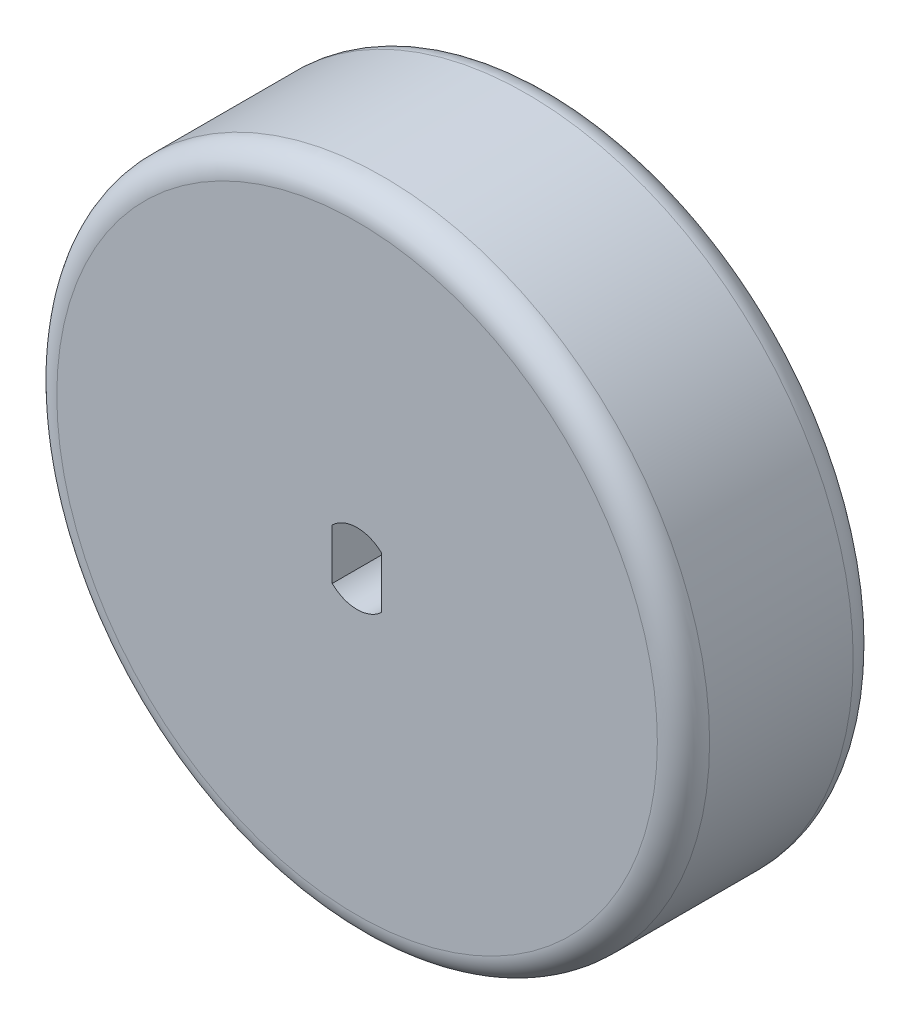
SolidWorks part; units mm, degrees
ref_plane "Front Plane" through (0, 0, 0) normal (0, 0, 1) x (1, 0, 0)
ref_plane "Top Plane" through (0, 0, 0) normal (0, 1, 0) x (1, 0, 0)
ref_plane "Right Plane" through (0, 0, 0) normal (1, 0, 0) x (0, 0, -1)
sketch "Sketch1" plane through (0, 0, 0) normal (0, 0, 1) x (1, 0, 0)
  line L0 (0, 0) -> (0, 25)
  circle A0 centre (0, 0) radius 25
  dimension "D1" = 50
extrude "Boss-Extrude1" add sketch "Sketch1" along normal blind 15 contours A0
fillet "Fillet1" radius 2 2 edges at (25, 0, 15) (25, 0, 0)
sketch "Sketch4" plane through (0, 0, 15) normal (0, 0, 1) x (1, 0, 0)
  line L0 (-1.903, 1.9412) -> (-1.903, -1.9412)
  line L1 (1.8591, 1.9833) -> (1.8591, -1.9833)
  arc A0 (1.8591, 1.9833) -> (-1.903, 1.9412) centre (0, 0) ccw
  arc A1 (-1.903, -1.9412) -> (1.8591, -1.9833) centre (0, 0) ccw
extrude "Cut-Extrude1" cut sketch "Sketch4" against normal blind 4
sketch "Sketch7" plane through (0, 0, 15) normal (0, 0, 1) x (1, 0, 0)
  circle A0 centre (0, 0) radius 1.04
extrude "Cut-Extrude2" cut sketch "Sketch7" against normal through all
